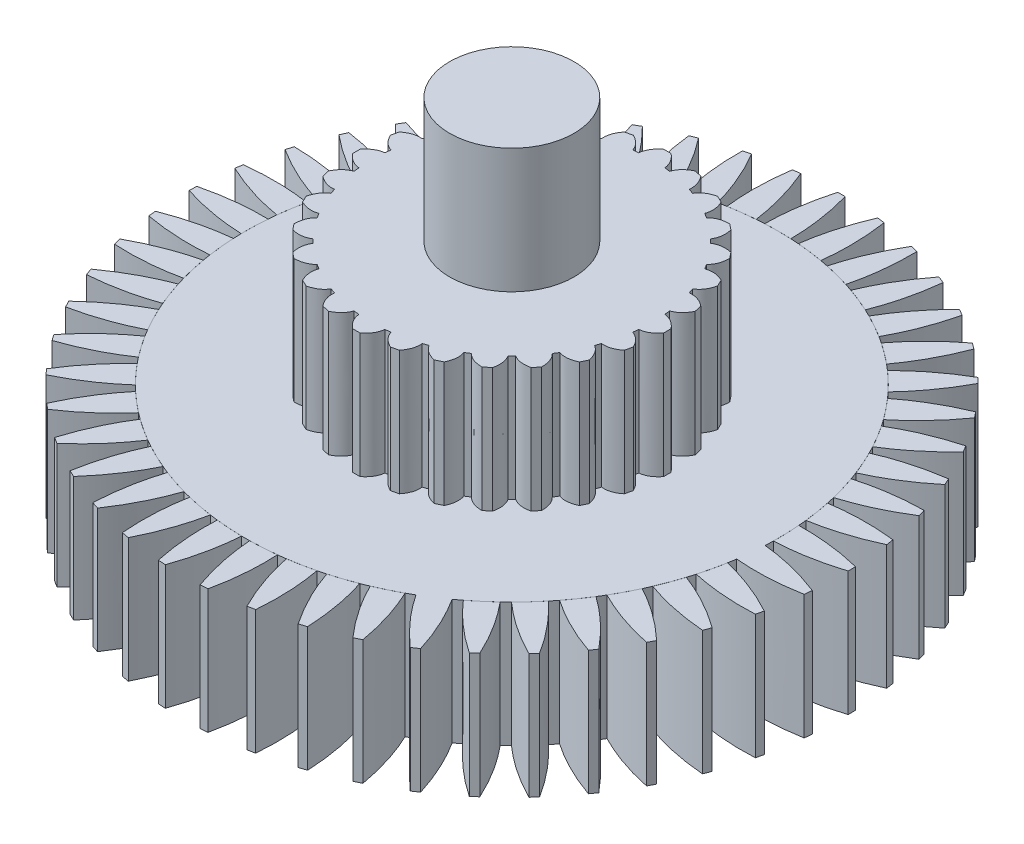
SolidWorks part; units mm, degrees
ref_plane "Front Plane" through (0, 0, 0) normal (0, 0, 1) x (1, 0, 0)
ref_plane "Top Plane" through (0, 0, 0) normal (0, 1, 0) x (1, 0, 0)
ref_plane "Right Plane" through (0, 0, 0) normal (1, 0, 0) x (0, 0, -1)
sketch "Sketch1" plane through (0, 0, 0) normal (0, 1, 0) x (1, 0, 0)
  line L0 (0, 2.5799) -> (0, -0.2416) construction
  line L1 (0.105, 2.4922) -> (0.105, 1.9026) construction
  line L2 (-0.03, 2.65) -> (0.03, 2.65)
  line L3 (0.3091, 2.6321) -> (0.3686, 2.6244)
  line L4 (0.6432, 2.5709) -> (0.7012, 2.5557)
  line L5 (0.9667, 2.4676) -> (1.0223, 2.4451)
  line L6 (1.2743, 2.3237) -> (1.3265, 2.2943)
  line L7 (1.561, 2.1417) -> (1.609, 2.1058)
  line L8 (1.822, 1.9245) -> (1.8651, 1.8828)
  line L9 (2.0531, 1.6757) -> (2.0906, 1.6288)
  line L10 (2.2506, 1.3994) -> (2.2817, 1.3481)
  line L11 (2.411, 1.1001) -> (2.4353, 1.0452)
  line L12 (2.5319, 0.7828) -> (2.549, 0.7252)
  line L13 (2.6112, 0.4526) -> (2.6208, 0.3933)
  line L14 (2.6477, 0.1149) -> (2.6496, 0.055)
  line L15 (2.6406, -0.2246) -> (2.6349, -0.2843)
  line L16 (2.5902, -0.5604) -> (2.5769, -0.6189)
  line L17 (2.4973, -0.8871) -> (2.4766, -0.9434)
  line L18 (2.3634, -1.1991) -> (2.3356, -1.2523)
  line L19 (2.1906, -1.4915) -> (2.1563, -1.5407)
  line L20 (1.9819, -1.7594) -> (1.9416, -1.8038)
  line L21 (1.7406, -1.9984) -> (1.695, -2.0373)
  line L22 (1.4708, -2.2046) -> (1.4205, -2.2373)
  line L23 (1.1768, -2.3746) -> (1.1228, -2.4006)
  line L24 (0.8635, -2.5055) -> (0.8066, -2.5245)
  line L25 (0.536, -2.5954) -> (0.4771, -2.6069)
  line L26 (0.1997, -2.6426) -> (0.1398, -2.6465)
  line L27 (-0.1398, -2.6465) -> (-0.1997, -2.6426)
  line L28 (-0.4771, -2.6069) -> (-0.536, -2.5954)
  line L29 (-0.8066, -2.5245) -> (-0.8635, -2.5055)
  line L30 (-1.1228, -2.4006) -> (-1.1768, -2.3746)
  line L31 (-1.4205, -2.2373) -> (-1.4708, -2.2046)
  line L32 (-1.695, -2.0373) -> (-1.7406, -1.9984)
  line L33 (-1.9416, -1.8038) -> (-1.9819, -1.7594)
  line L34 (-2.1563, -1.5407) -> (-2.1906, -1.4915)
  line L35 (-2.3356, -1.2523) -> (-2.3634, -1.1991)
  line L36 (-2.4766, -0.9434) -> (-2.4973, -0.8871)
  line L37 (-2.5769, -0.6189) -> (-2.5902, -0.5604)
  line L38 (-2.6349, -0.2843) -> (-2.6406, -0.2246)
  line L39 (-2.6496, 0.055) -> (-2.6477, 0.1149)
  line L40 (-2.6208, 0.3933) -> (-2.6112, 0.4526)
  line L41 (-2.549, 0.7252) -> (-2.5319, 0.7828)
  line L42 (-2.4353, 1.0452) -> (-2.411, 1.1001)
  line L43 (-2.2817, 1.3481) -> (-2.2506, 1.3994)
  line L44 (-2.0906, 1.6288) -> (-2.0531, 1.6757)
  line L45 (-1.8651, 1.8828) -> (-1.822, 1.9245)
  line L46 (-1.609, 2.1058) -> (-1.561, 2.1417)
  line L47 (-1.3265, 2.2943) -> (-1.2743, 2.3237)
  line L48 (-1.0223, 2.4451) -> (-0.9667, 2.4676)
  line L49 (-0.7012, 2.5557) -> (-0.6432, 2.5709)
  line L50 (-0.3686, 2.6244) -> (-0.3091, 2.6321)
  circle A0 centre (0, 0) radius 2.14
  spline S0 degree 2 poles (0.03, 2.65) (0.1023, 2.3962) (0.105, 2.1374) knots 0 0 0 0.927528 0.927528 0.927528
  spline S1 degree 1 poles (0, 2.14) (0.105, 2.1374) knots 0 0 1 1
  spline S2 degree 1 poles (0, 2.14) (-0.105, 2.1374) knots 0 0 1 1
  spline S3 degree 2 poles (-0.03, 2.65) (-0.1023, 2.3962) (-0.105, 2.1374) knots 0 0 0 0.927528 0.927528 0.927528
  spline S4 degree 1 poles (0.2737, 2.1224) (0.1692, 2.1333) knots 0 0 1 1
  spline S5 degree 1 poles (0.2737, 2.1224) (0.3775, 2.1064) knots 0 0 1 1
  spline S6 degree 2 poles (0.3091, 2.6321) (0.205, 2.3896) (0.1692, 2.1333) knots 0 0 0 0.927528 0.927528 0.927528
  spline S7 degree 2 poles (0.3686, 2.6244) (0.4079, 2.3635) (0.3775, 2.1064) knots 0 0 0 0.927528 0.927528 0.927528
  spline S8 degree 1 poles (0.5428, 2.07) (0.4406, 2.0942) knots 0 0 1 1
  spline S9 degree 1 poles (0.5428, 2.07) (0.6437, 2.0409) knots 0 0 1 1
  spline S10 degree 2 poles (0.6432, 2.5709) (0.5089, 2.3438) (0.4406, 2.0942) knots 0 0 0 0.927528 0.927528 0.927528
  spline S11 degree 2 poles (0.7012, 2.5557) (0.7068, 2.2919) (0.6437, 2.0409) knots 0 0 0 0.927528 0.927528 0.927528
  spline S12 degree 1 poles (0.8031, 1.9836) (0.7048, 2.0206) knots 0 0 1 1
  spline S13 degree 1 poles (0.8031, 1.9836) (0.8994, 1.9418) knots 0 0 1 1
  spline S14 degree 2 poles (0.9667, 2.4676) (0.8044, 2.2595) (0.7048, 2.0206) knots 0 0 0 0.927528 0.927528 0.927528
  spline S15 degree 2 poles (1.0223, 2.4451) (0.994, 2.1827) (0.8994, 1.9418) knots 0 0 0 0.927528 0.927528 0.927528
  spline S16 degree 1 poles (1.0501, 1.8646) (0.9574, 1.9139) knots 0 0 1 1
  spline S17 degree 1 poles (1.0501, 1.8646) (1.1404, 1.8109) knots 0 0 1 1
  spline S18 degree 2 poles (1.2743, 2.3237) (1.0868, 2.1381) (0.9574, 1.9139) knots 0 0 0 0.927528 0.927528 0.927528
  spline S19 degree 2 poles (1.3265, 2.2943) (1.265, 2.0377) (1.1404, 1.8109) knots 0 0 0 0.927528 0.927528 0.927528
  spline S20 degree 1 poles (1.28, 1.715) (1.1943, 1.7758) knots 0 0 1 1
  spline S21 degree 1 poles (1.28, 1.715) (1.3626, 1.6502) knots 0 0 1 1
  spline S22 degree 2 poles (1.561, 2.1417) (1.3512, 1.9816) (1.1943, 1.7758) knots 0 0 0 0.927528 0.927528 0.927528
  spline S23 degree 2 poles (1.609, 2.1058) (1.5152, 1.8592) (1.3626, 1.6502) knots 0 0 0 0.927528 0.927528 0.927528
  spline S24 degree 1 poles (1.4888, 1.5373) (1.4115, 1.6085) knots 0 0 1 1
  spline S25 degree 1 poles (1.4888, 1.5373) (1.5624, 1.4624) knots 0 0 1 1
  spline S26 degree 2 poles (1.822, 1.9245) (1.5935, 1.7925) (1.4115, 1.6085) knots 0 0 0 0.927528 0.927528 0.927528
  spline S27 degree 2 poles (1.8651, 1.8828) (1.7405, 1.6502) (1.5624, 1.4624) knots 0 0 0 0.927528 0.927528 0.927528
  spline S28 degree 1 poles (1.6731, 1.3343) (1.6056, 1.4148) knots 0 0 1 1
  spline S29 degree 1 poles (1.6731, 1.3343) (1.7366, 1.2506) knots 0 0 1 1
  spline S30 degree 2 poles (2.0531, 1.6757) (1.8097, 1.574) (1.6056, 1.4148) knots 0 0 0 0.927528 0.927528 0.927528
  spline S31 degree 2 poles (2.0906, 1.6288) (1.9372, 1.4141) (1.7366, 1.2506) knots 0 0 0 0.927528 0.927528 0.927528
  spline S32 degree 1 poles (1.83, 1.1094) (1.7734, 1.1978) knots 0 0 1 1
  spline S33 degree 1 poles (1.83, 1.1094) (1.8822, 1.0182) knots 0 0 1 1
  spline S34 degree 2 poles (2.2506, 1.3994) (1.9961, 1.3297) (1.7734, 1.1978) knots 0 0 0 0.927528 0.927528 0.927528
  spline S35 degree 2 poles (2.2817, 1.3481) (2.1022, 1.1547) (1.8822, 1.0182) knots 0 0 0 0.927528 0.927528 0.927528
  spline S36 degree 1 poles (1.9568, 0.8662) (1.912, 0.9612) knots 0 0 1 1
  spline S37 degree 1 poles (1.9568, 0.8662) (1.997, 0.7692) knots 0 0 1 1
  spline S38 degree 2 poles (2.411, 1.1001) (2.1498, 1.0635) (1.912, 0.9612) knots 0 0 0 0.927528 0.927528 0.927528
  spline S39 degree 2 poles (2.4353, 1.0452) (2.2326, 0.8764) (1.997, 0.7692) knots 0 0 0 0.927528 0.927528 0.927528
  spline S40 degree 1 poles (2.0515, 0.6089) (2.0192, 0.7088) knots 0 0 1 1
  spline S41 degree 1 poles (2.0515, 0.6089) (2.079, 0.5075) knots 0 0 1 1
  spline S42 degree 2 poles (2.5319, 0.7828) (2.2681, 0.7799) (2.0192, 0.7088) knots 0 0 0 0.927528 0.927528 0.927528
  spline S43 degree 2 poles (2.549, 0.7252) (2.3263, 0.5837) (2.079, 0.5075) knots 0 0 0 0.927528 0.927528 0.927528
  spline S44 degree 1 poles (2.1126, 0.3415) (2.0933, 0.4448) knots 0 0 1 1
  spline S45 degree 1 poles (2.1126, 0.3415) (2.1268, 0.2375) knots 0 0 1 1
  spline S46 degree 2 poles (2.6112, 0.4526) (2.3492, 0.4834) (2.0933, 0.4448) knots 0 0 0 0.927528 0.927528 0.927528
  spline S47 degree 2 poles (2.6208, 0.3933) (2.3819, 0.2815) (2.1268, 0.2375) knots 0 0 0 0.927528 0.927528 0.927528
  spline S48 degree 1 poles (2.1389, 0.0686) (2.133, 0.1735) knots 0 0 1 1
  spline S49 degree 1 poles (2.1389, 0.0686) (2.1397, -0.0364) knots 0 0 1 1
  spline S50 degree 2 poles (2.6477, 0.1149) (2.3917, 0.179) (2.133, 0.1735) knots 0 0 0 0.927528 0.927528 0.927528
  spline S51 degree 2 poles (2.6496, 0.055) (2.3983, -0.0254) (2.1397, -0.0364) knots 0 0 0 0.927528 0.927528 0.927528
  spline S52 degree 1 poles (2.1301, -0.2055) (2.1376, -0.1007) knots 0 0 1 1
  spline S53 degree 1 poles (2.1301, -0.2055) (2.1175, -0.3098) knots 0 0 1 1
  spline S54 degree 2 poles (2.6406, -0.2246) (2.395, -0.1283) (2.1376, -0.1007) knots 0 0 0 0.927528 0.927528 0.927528
  spline S55 degree 2 poles (2.6349, -0.2843) (2.3753, -0.3319) (2.1175, -0.3098) knots 0 0 0 0.927528 0.927528 0.927528
  spline S56 degree 1 poles (2.0863, -0.4762) (2.1072, -0.3733) knots 0 0 1 1
  spline S57 degree 1 poles (2.0863, -0.4762) (2.0605, -0.578) knots 0 0 1 1
  spline S58 degree 2 poles (2.5902, -0.5604) (2.3589, -0.4335) (2.1072, -0.3733) knots 0 0 0 0.927528 0.927528 0.927528
  spline S59 degree 2 poles (2.5769, -0.6189) (2.3134, -0.6329) (2.0605, -0.578) knots 0 0 0 0.927528 0.927528 0.927528
  spline S60 degree 1 poles (2.0083, -0.7391) (2.0422, -0.6397) knots 0 0 1 1
  spline S61 degree 1 poles (2.0083, -0.7391) (1.9696, -0.8367) knots 0 0 1 1
  spline S62 degree 2 poles (2.4973, -0.8871) (2.2841, -0.7316) (2.0422, -0.6397) knots 0 0 0 0.927528 0.927528 0.927528
  spline S63 degree 2 poles (2.4766, -0.9434) (2.2135, -0.9236) (1.9696, -0.8367) knots 0 0 0 0.927528 0.927528 0.927528
  spline S64 degree 1 poles (1.8973, -0.9898) (1.9436, -0.8955) knots 0 0 1 1
  spline S65 degree 1 poles (1.8973, -0.9898) (1.8465, -1.0817) knots 0 0 1 1
  spline S66 degree 2 poles (2.3634, -1.1991) (2.1718, -1.0177) (1.9436, -0.8955) knots 0 0 0 0.927528 0.927528 0.927528
  spline S67 degree 2 poles (2.3356, -1.2523) (2.0772, -1.199) (1.8465, -1.0817) knots 0 0 0 0.927528 0.927528 0.927528
  spline S68 degree 1 poles (1.7552, -1.2243) (1.8131, -1.1367) knots 0 0 1 1
  spline S69 degree 1 poles (1.7552, -1.2243) (1.693, -1.309) knots 0 0 1 1
  spline S70 degree 2 poles (2.1906, -1.4915) (2.0238, -1.287) (1.8131, -1.1367) knots 0 0 0 0.927528 0.927528 0.927528
  spline S71 degree 2 poles (2.1563, -1.5407) (1.9068, -1.4548) (1.693, -1.309) knots 0 0 0 0.927528 0.927528 0.927528
  spline S72 degree 1 poles (1.5842, -1.4387) (1.6529, -1.3593) knots 0 0 1 1
  spline S73 degree 1 poles (1.5842, -1.4387) (1.5117, -1.5147) knots 0 0 1 1
  spline S74 degree 2 poles (1.9819, -1.7594) (1.8427, -1.5353) (1.6529, -1.3593) knots 0 0 0 0.927528 0.927528 0.927528
  spline S75 degree 2 poles (1.9416, -1.8038) (1.7051, -1.6867) (1.5117, -1.5147) knots 0 0 0 0.927528 0.927528 0.927528
  spline S76 degree 1 poles (1.3872, -1.6295) (1.4655, -1.5595) knots 0 0 1 1
  spline S77 degree 1 poles (1.3872, -1.6295) (1.3056, -1.6956) knots 0 0 1 1
  spline S78 degree 2 poles (1.7406, -1.9984) (1.6312, -1.7583) (1.4655, -1.5595) knots 0 0 0 0.927528 0.927528 0.927528
  spline S79 degree 2 poles (1.695, -2.0373) (1.4754, -1.8909) (1.3056, -1.6956) knots 0 0 0 0.927528 0.927528 0.927528
  spline S80 degree 1 poles (1.1674, -1.7935) (1.254, -1.7341) knots 0 0 1 1
  spline S81 degree 1 poles (1.1674, -1.7935) (1.078, -1.8486) knots 0 0 1 1
  spline S82 degree 2 poles (1.4708, -2.2046) (1.393, -1.9525) (1.254, -1.7341) knots 0 0 0 0.927528 0.927528 0.927528
  spline S83 degree 2 poles (1.4205, -2.2373) (1.2215, -2.0641) (1.078, -1.8486) knots 0 0 0 0.927528 0.927528 0.927528
  spline S84 degree 1 poles (0.9285, -1.9281) (1.022, -1.8802) knots 0 0 1 1
  spline S85 degree 1 poles (0.9285, -1.9281) (0.8328, -1.9713) knots 0 0 1 1
  spline S86 degree 2 poles (1.1768, -2.3746) (1.1318, -2.1146) (1.022, -1.8802) knots 0 0 0 0.927528 0.927528 0.927528
  spline S87 degree 2 poles (1.1228, -2.4006) (0.9475, -2.2033) (0.8328, -1.9713) knots 0 0 0 0.927528 0.927528 0.927528
  spline S88 degree 1 poles (0.6743, -2.031) (0.7732, -1.9954) knots 0 0 1 1
  spline S89 degree 1 poles (0.6743, -2.031) (0.5739, -2.0616) knots 0 0 1 1
  spline S90 degree 2 poles (0.8635, -2.5055) (0.8521, -2.2419) (0.7732, -1.9954) knots 0 0 0 0.927528 0.927528 0.927528
  spline S91 degree 2 poles (0.8066, -2.5245) (0.658, -2.3064) (0.5739, -2.0616) knots 0 0 0 0.927528 0.927528 0.927528
  spline S92 degree 1 poles (0.4091, -2.1005) (0.5117, -2.0779) knots 0 0 1 1
  spline S93 degree 1 poles (0.4091, -2.1005) (0.3055, -2.1181) knots 0 0 1 1
  spline S94 degree 2 poles (0.536, -2.5954) (0.5585, -2.3325) (0.5117, -2.0779) knots 0 0 0 0.927528 0.927528 0.927528
  spline S95 degree 2 poles (0.4771, -2.6069) (0.3577, -2.3716) (0.3055, -2.1181) knots 0 0 0 0.927528 0.927528 0.927528
  spline S96 degree 1 poles (0.1371, -2.1356) (0.2417, -2.1263) knots 0 0 1 1
  spline S97 degree 1 poles (0.1371, -2.1356) (0.0322, -2.1398) knots 0 0 1 1
  spline S98 degree 2 poles (0.1997, -2.6426) (0.2556, -2.3848) (0.2417, -2.1263) knots 0 0 0 0.927528 0.927528 0.927528
  spline S99 degree 2 poles (0.1398, -2.6465) (0.0515, -2.3979) (0.0322, -2.1398) knots 0 0 0 0.927528 0.927528 0.927528
  spline S100 degree 1 poles (-0.1371, -2.1356) (-0.0322, -2.1398) knots 0 0 1 1
  spline S101 degree 1 poles (-0.1371, -2.1356) (-0.2417, -2.1263) knots 0 0 1 1
  spline S102 degree 2 poles (-0.1398, -2.6465) (-0.0515, -2.3979) (-0.0322, -2.1398) knots 0 0 0 0.927528 0.927528 0.927528
  spline S103 degree 2 poles (-0.1997, -2.6426) (-0.2556, -2.3848) (-0.2417, -2.1263) knots 0 0 0 0.927528 0.927528 0.927528
  spline S104 degree 1 poles (-0.4091, -2.1005) (-0.3055, -2.1181) knots 0 0 1 1
  spline S105 degree 1 poles (-0.4091, -2.1005) (-0.5117, -2.0779) knots 0 0 1 1
  spline S106 degree 2 poles (-0.4771, -2.6069) (-0.3577, -2.3716) (-0.3055, -2.1181) knots 0 0 0 0.927528 0.927528 0.927528
  spline S107 degree 2 poles (-0.536, -2.5954) (-0.5585, -2.3325) (-0.5117, -2.0779) knots 0 0 0 0.927528 0.927528 0.927528
  spline S108 degree 1 poles (-0.6743, -2.031) (-0.5739, -2.0616) knots 0 0 1 1
  spline S109 degree 1 poles (-0.6743, -2.031) (-0.7732, -1.9954) knots 0 0 1 1
  spline S110 degree 2 poles (-0.8066, -2.5245) (-0.658, -2.3064) (-0.5739, -2.0616) knots 0 0 0 0.927528 0.927528 0.927528
  spline S111 degree 2 poles (-0.8635, -2.5055) (-0.8521, -2.2419) (-0.7732, -1.9954) knots 0 0 0 0.927528 0.927528 0.927528
  spline S112 degree 1 poles (-0.9285, -1.9281) (-0.8328, -1.9713) knots 0 0 1 1
  spline S113 degree 1 poles (-0.9285, -1.9281) (-1.022, -1.8802) knots 0 0 1 1
  spline S114 degree 2 poles (-1.1228, -2.4006) (-0.9475, -2.2033) (-0.8328, -1.9713) knots 0 0 0 0.927528 0.927528 0.927528
  spline S115 degree 2 poles (-1.1768, -2.3746) (-1.1318, -2.1146) (-1.022, -1.8802) knots 0 0 0 0.927528 0.927528 0.927528
  spline S116 degree 1 poles (-1.1674, -1.7935) (-1.078, -1.8486) knots 0 0 1 1
  spline S117 degree 1 poles (-1.1674, -1.7935) (-1.254, -1.7341) knots 0 0 1 1
  spline S118 degree 2 poles (-1.4205, -2.2373) (-1.2215, -2.0641) (-1.078, -1.8486) knots 0 0 0 0.927528 0.927528 0.927528
  spline S119 degree 2 poles (-1.4708, -2.2046) (-1.393, -1.9525) (-1.254, -1.7341) knots 0 0 0 0.927528 0.927528 0.927528
  spline S120 degree 1 poles (-1.3872, -1.6295) (-1.3056, -1.6956) knots 0 0 1 1
  spline S121 degree 1 poles (-1.3872, -1.6295) (-1.4655, -1.5595) knots 0 0 1 1
  spline S122 degree 2 poles (-1.695, -2.0373) (-1.4754, -1.8909) (-1.3056, -1.6956) knots 0 0 0 0.927528 0.927528 0.927528
  spline S123 degree 2 poles (-1.7406, -1.9984) (-1.6312, -1.7583) (-1.4655, -1.5595) knots 0 0 0 0.927528 0.927528 0.927528
  spline S124 degree 1 poles (-1.5842, -1.4387) (-1.5117, -1.5147) knots 0 0 1 1
  spline S125 degree 1 poles (-1.5842, -1.4387) (-1.6529, -1.3593) knots 0 0 1 1
  spline S126 degree 2 poles (-1.9416, -1.8038) (-1.7051, -1.6867) (-1.5117, -1.5147) knots 0 0 0 0.927528 0.927528 0.927528
  spline S127 degree 2 poles (-1.9819, -1.7594) (-1.8427, -1.5353) (-1.6529, -1.3593) knots 0 0 0 0.927528 0.927528 0.927528
  spline S128 degree 1 poles (-1.7552, -1.2243) (-1.693, -1.309) knots 0 0 1 1
  spline S129 degree 1 poles (-1.7552, -1.2243) (-1.8131, -1.1367) knots 0 0 1 1
  spline S130 degree 2 poles (-2.1563, -1.5407) (-1.9068, -1.4548) (-1.693, -1.309) knots 0 0 0 0.927528 0.927528 0.927528
  spline S131 degree 2 poles (-2.1906, -1.4915) (-2.0238, -1.287) (-1.8131, -1.1367) knots 0 0 0 0.927528 0.927528 0.927528
  spline S132 degree 1 poles (-1.8973, -0.9898) (-1.8465, -1.0817) knots 0 0 1 1
  spline S133 degree 1 poles (-1.8973, -0.9898) (-1.9436, -0.8955) knots 0 0 1 1
  spline S134 degree 2 poles (-2.3356, -1.2523) (-2.0772, -1.199) (-1.8465, -1.0817) knots 0 0 0 0.927528 0.927528 0.927528
  spline S135 degree 2 poles (-2.3634, -1.1991) (-2.1718, -1.0177) (-1.9436, -0.8955) knots 0 0 0 0.927528 0.927528 0.927528
  spline S136 degree 1 poles (-2.0083, -0.7391) (-1.9696, -0.8367) knots 0 0 1 1
  spline S137 degree 1 poles (-2.0083, -0.7391) (-2.0422, -0.6397) knots 0 0 1 1
  spline S138 degree 2 poles (-2.4766, -0.9434) (-2.2135, -0.9236) (-1.9696, -0.8367) knots 0 0 0 0.927528 0.927528 0.927528
  spline S139 degree 2 poles (-2.4973, -0.8871) (-2.2841, -0.7316) (-2.0422, -0.6397) knots 0 0 0 0.927528 0.927528 0.927528
  spline S140 degree 1 poles (-2.0863, -0.4762) (-2.0605, -0.578) knots 0 0 1 1
  spline S141 degree 1 poles (-2.0863, -0.4762) (-2.1072, -0.3733) knots 0 0 1 1
  spline S142 degree 2 poles (-2.5769, -0.6189) (-2.3134, -0.6329) (-2.0605, -0.578) knots 0 0 0 0.927528 0.927528 0.927528
  spline S143 degree 2 poles (-2.5902, -0.5604) (-2.3589, -0.4335) (-2.1072, -0.3733) knots 0 0 0 0.927528 0.927528 0.927528
  spline S144 degree 1 poles (-2.1301, -0.2055) (-2.1175, -0.3098) knots 0 0 1 1
  spline S145 degree 1 poles (-2.1301, -0.2055) (-2.1376, -0.1007) knots 0 0 1 1
  spline S146 degree 2 poles (-2.6349, -0.2843) (-2.3753, -0.3319) (-2.1175, -0.3098) knots 0 0 0 0.927528 0.927528 0.927528
  spline S147 degree 2 poles (-2.6406, -0.2246) (-2.395, -0.1283) (-2.1376, -0.1007) knots 0 0 0 0.927528 0.927528 0.927528
  spline S148 degree 1 poles (-2.1389, 0.0686) (-2.1397, -0.0364) knots 0 0 1 1
  spline S149 degree 1 poles (-2.1389, 0.0686) (-2.133, 0.1735) knots 0 0 1 1
  spline S150 degree 2 poles (-2.6496, 0.055) (-2.3983, -0.0254) (-2.1397, -0.0364) knots 0 0 0 0.927528 0.927528 0.927528
  spline S151 degree 2 poles (-2.6477, 0.1149) (-2.3917, 0.179) (-2.133, 0.1735) knots 0 0 0 0.927528 0.927528 0.927528
  spline S152 degree 1 poles (-2.1126, 0.3415) (-2.1268, 0.2375) knots 0 0 1 1
  spline S153 degree 1 poles (-2.1126, 0.3415) (-2.0933, 0.4448) knots 0 0 1 1
  spline S154 degree 2 poles (-2.6208, 0.3933) (-2.3819, 0.2815) (-2.1268, 0.2375) knots 0 0 0 0.927528 0.927528 0.927528
  spline S155 degree 2 poles (-2.6112, 0.4526) (-2.3492, 0.4834) (-2.0933, 0.4448) knots 0 0 0 0.927528 0.927528 0.927528
  spline S156 degree 1 poles (-2.0515, 0.6089) (-2.079, 0.5075) knots 0 0 1 1
  spline S157 degree 1 poles (-2.0515, 0.6089) (-2.0192, 0.7088) knots 0 0 1 1
  spline S158 degree 2 poles (-2.549, 0.7252) (-2.3263, 0.5837) (-2.079, 0.5075) knots 0 0 0 0.927528 0.927528 0.927528
  spline S159 degree 2 poles (-2.5319, 0.7828) (-2.2681, 0.7799) (-2.0192, 0.7088) knots 0 0 0 0.927528 0.927528 0.927528
  spline S160 degree 1 poles (-1.9568, 0.8662) (-1.997, 0.7692) knots 0 0 1 1
  spline S161 degree 1 poles (-1.9568, 0.8662) (-1.912, 0.9612) knots 0 0 1 1
  spline S162 degree 2 poles (-2.4353, 1.0452) (-2.2326, 0.8764) (-1.997, 0.7692) knots 0 0 0 0.927528 0.927528 0.927528
  spline S163 degree 2 poles (-2.411, 1.1001) (-2.1498, 1.0635) (-1.912, 0.9612) knots 0 0 0 0.927528 0.927528 0.927528
  spline S164 degree 1 poles (-1.83, 1.1094) (-1.8822, 1.0182) knots 0 0 1 1
  spline S165 degree 1 poles (-1.83, 1.1094) (-1.7734, 1.1978) knots 0 0 1 1
  spline S166 degree 2 poles (-2.2817, 1.3481) (-2.1022, 1.1547) (-1.8822, 1.0182) knots 0 0 0 0.927528 0.927528 0.927528
  spline S167 degree 2 poles (-2.2506, 1.3994) (-1.9961, 1.3297) (-1.7734, 1.1978) knots 0 0 0 0.927528 0.927528 0.927528
  spline S168 degree 1 poles (-1.6731, 1.3343) (-1.7366, 1.2506) knots 0 0 1 1
  spline S169 degree 1 poles (-1.6731, 1.3343) (-1.6056, 1.4148) knots 0 0 1 1
  spline S170 degree 2 poles (-2.0906, 1.6288) (-1.9372, 1.4141) (-1.7366, 1.2506) knots 0 0 0 0.927528 0.927528 0.927528
  spline S171 degree 2 poles (-2.0531, 1.6757) (-1.8097, 1.574) (-1.6056, 1.4148) knots 0 0 0 0.927528 0.927528 0.927528
  spline S172 degree 1 poles (-1.4888, 1.5373) (-1.5624, 1.4624) knots 0 0 1 1
  spline S173 degree 1 poles (-1.4888, 1.5373) (-1.4115, 1.6085) knots 0 0 1 1
  spline S174 degree 2 poles (-1.8651, 1.8828) (-1.7405, 1.6502) (-1.5624, 1.4624) knots 0 0 0 0.927528 0.927528 0.927528
  spline S175 degree 2 poles (-1.822, 1.9245) (-1.5935, 1.7925) (-1.4115, 1.6085) knots 0 0 0 0.927528 0.927528 0.927528
  spline S176 degree 1 poles (-1.28, 1.715) (-1.3626, 1.6502) knots 0 0 1 1
  spline S177 degree 1 poles (-1.28, 1.715) (-1.1943, 1.7758) knots 0 0 1 1
  spline S178 degree 2 poles (-1.609, 2.1058) (-1.5152, 1.8592) (-1.3626, 1.6502) knots 0 0 0 0.927528 0.927528 0.927528
  spline S179 degree 2 poles (-1.561, 2.1417) (-1.3512, 1.9816) (-1.1943, 1.7758) knots 0 0 0 0.927528 0.927528 0.927528
  spline S180 degree 1 poles (-1.0501, 1.8646) (-1.1404, 1.8109) knots 0 0 1 1
  spline S181 degree 1 poles (-1.0501, 1.8646) (-0.9574, 1.9139) knots 0 0 1 1
  spline S182 degree 2 poles (-1.3265, 2.2943) (-1.265, 2.0377) (-1.1404, 1.8109) knots 0 0 0 0.927528 0.927528 0.927528
  spline S183 degree 2 poles (-1.2743, 2.3237) (-1.0868, 2.1381) (-0.9574, 1.9139) knots 0 0 0 0.927528 0.927528 0.927528
  spline S184 degree 1 poles (-0.8031, 1.9836) (-0.8994, 1.9418) knots 0 0 1 1
  spline S185 degree 1 poles (-0.8031, 1.9836) (-0.7048, 2.0206) knots 0 0 1 1
  spline S186 degree 2 poles (-1.0223, 2.4451) (-0.994, 2.1827) (-0.8994, 1.9418) knots 0 0 0 0.927528 0.927528 0.927528
  spline S187 degree 2 poles (-0.9667, 2.4676) (-0.8044, 2.2595) (-0.7048, 2.0206) knots 0 0 0 0.927528 0.927528 0.927528
  spline S188 degree 1 poles (-0.5428, 2.07) (-0.6437, 2.0409) knots 0 0 1 1
  spline S189 degree 1 poles (-0.5428, 2.07) (-0.4406, 2.0942) knots 0 0 1 1
  spline S190 degree 2 poles (-0.7012, 2.5557) (-0.7068, 2.2919) (-0.6437, 2.0409) knots 0 0 0 0.927528 0.927528 0.927528
  spline S191 degree 2 poles (-0.6432, 2.5709) (-0.5089, 2.3438) (-0.4406, 2.0942) knots 0 0 0 0.927528 0.927528 0.927528
  spline S192 degree 1 poles (-0.2737, 2.1224) (-0.3775, 2.1064) knots 0 0 1 1
  spline S193 degree 1 poles (-0.2737, 2.1224) (-0.1692, 2.1333) knots 0 0 1 1
  spline S194 degree 2 poles (-0.3686, 2.6244) (-0.4079, 2.3635) (-0.3775, 2.1064) knots 0 0 0 0.927528 0.927528 0.927528
  spline S195 degree 2 poles (-0.3091, 2.6321) (-0.205, 2.3896) (-0.1692, 2.1333) knots 0 0 0 0.927528 0.927528 0.927528
  point P13 (0, 2.65)
  dimension "D1" = 4.28
  dimension "D2" = 0.105
  dimension "D3" = 0.03
  dimension "D4" = 2.65
  dimension "D5" = 49
extrude "Boss-Extrude1" add sketch "Sketch1" along normal blind 1 contours S193 S192 A0 S189 S188 S185 S184 S181 S180 S177 S176 S173 S172 S169 S168 S165 S164 S161 S160 S157 S156 S153 S152 S149 S148 S145 S144 S141 S140 S137 S136 S133 S132 S129 S128 | S87 L23 S86 A0 | S79 L21 S78 A0 | S75 L20 S74 A0 | S71 L19 S70 A0 | S67 L18 S66 A0 | S63 L17 S62 A0 | S59 L16 S58 A0 | S51 L14 S50 A0 | S47 L13 S46 A0 | S43 L12 S42 A0 | S39 L11 S38 A0 | S35 L10 S34 A0 | S31 L9 S30 A0 | S27 L8 S26 A0 | S23 L7 S22 A0 | S19 L6 S18 A0 | S15 L5 S14 A0 | S91 L24 S90 A0 | S95 L25 S94 A0 | S99 L26 S98 A0 | S103 L27 S102 A0 | S107 L28 S106 A0 | S111 L29 S110 A0 | S115 L30 S114 A0 | S119 L31 S118 A0 | S123 L32 S122 A0 | S127 L33 S126 A0 | S131 L34 S130 A0 | S135 L35 S134 A0 | S139 L36 S138 A0 | S143 L37 S142 A0 | S147 L38 S146 A0 | S151 L39 S150 A0 | S155 L40 S154 A0 | S159 L41 S158 A0 | S163 L42 S162 A0 | S167 L43 S166 A0 | S171 L44 S170 A0 | S175 L45 S174 A0 | S179 L46 S178 A0 | S183 L47 S182 A0 | S187 L48 S186 A0 | S191 L49 S190 A0 | S195 L50 S194 A0 | S11 L4 S10 A0 | S7 L3 S6 A0 | L2 S3 A0 S0 | S83 S81 S80 S82 L22 | S54 S52 S53 S55 L15 region at (0, 0, -2.3543) region at (0, 0, 0) region at (-0.3011, 0, -2.335) region at (0.3011, 0, -2.335) region at (-0.5972, 0, -2.2773) region at (0.5972, 0, -2.2773) region at (-0.8835, 0, -2.1822) region at (0.8835, 0, -2.1822) region at (-1.1553, 0, -2.0513) region at (1.1553, 0, -2.0513) region at (-1.4081, 0, -1.8868) region at (1.4081, 0, -1.8868) region at (-1.6378, 0, -1.6912) region at (1.6378, 0, -1.6912) region at (-1.8407, 0, -1.4679) region at (1.8407, 0, -1.4679) region at (-2.0133, 0, -1.2205) region at (2.0133, 0, -1.2205) region at (-2.1528, 0, -0.953) region at (2.1528, 0, -0.953) region at (-2.257, 0, -0.6699) region at (2.257, 0, -0.6699) region at (-2.3241, 0, -0.3757) region at (2.3241, 0, -0.3757) region at (-2.3531, 0, -0.0755) region at (2.3531, 0, -0.0755) region at (-2.3434, 0, 0.2261) region at (-2.2953, 0, 0.5239) region at (2.2953, 0, 0.5239) region at (-2.2094, 0, 0.8131) region at (2.2094, 0, 0.8131) region at (-2.0873, 0, 1.089) region at (2.0873, 0, 1.089) region at (-1.9309, 0, 1.3469) region at (1.9309, 0, 1.3469) region at (-1.7428, 0, 1.5828) region at (1.7428, 0, 1.5828) region at (-1.5261, 0, 1.7927) region at (1.5261, 0, 1.7927) region at (-1.2844, 0, 1.9731) region at (-1.0215, 0, 2.1212) region at (1.0215, 0, 2.1212) region at (-0.7419, 0, 2.2344) region at (0.7419, 0, 2.2344) region at (-0.45, 0, 2.3109) region at (0.45, 0, 2.3109) region at (-0.1508, 0, 2.3495) region at (0.1508, 0, 2.3495)
sketch "Sketch2" plane through (0, 1, 0) normal (0, 1, 0) x (1, 0, 0)
  circle A1 centre (0, 0) radius 1.13
  dimension "D1" = 2.26
extrude "Boss-Extrude11" add sketch "Sketch2" along normal blind 1
sketch "Sketch3" plane through (0, 2, 0) normal (0, 1, 0) x (1, 0, 0)
  line L0 (0, 1.3367) -> (0, 0.8013) construction
  line L1 (0.105, 1.2872) -> (0.105, 0.9526) construction
  line L2 (-0.03, 1.25) -> (0.03, 1.25)
  line L3 (0.2489, 1.2253) -> (0.3074, 1.212)
  line L4 (0.5153, 1.1392) -> (0.5694, 1.1132)
  line L5 (0.7559, 0.996) -> (0.8028, 0.9586)
  line L6 (0.9586, 0.8028) -> (0.996, 0.7559)
  line L7 (1.1132, 0.5694) -> (1.1392, 0.5153)
  line L8 (1.212, 0.3074) -> (1.2253, 0.2489)
  line L9 (1.25, 0.03) -> (1.25, -0.03)
  line L10 (1.2253, -0.2489) -> (1.212, -0.3074)
  line L11 (1.1392, -0.5153) -> (1.1132, -0.5694)
  line L12 (0.996, -0.7559) -> (0.9586, -0.8028)
  line L13 (0.8028, -0.9586) -> (0.7559, -0.996)
  line L14 (0.5694, -1.1132) -> (0.5153, -1.1392)
  line L15 (0.3074, -1.212) -> (0.2489, -1.2253)
  line L16 (0.03, -1.25) -> (-0.03, -1.25)
  line L17 (-0.2489, -1.2253) -> (-0.3074, -1.212)
  line L18 (-0.5153, -1.1392) -> (-0.5694, -1.1132)
  line L19 (-0.7559, -0.996) -> (-0.8028, -0.9586)
  line L20 (-0.9586, -0.8028) -> (-0.996, -0.7559)
  line L21 (-1.1132, -0.5694) -> (-1.1392, -0.5153)
  line L22 (-1.212, -0.3074) -> (-1.2253, -0.2489)
  line L23 (-1.25, -0.03) -> (-1.25, 0.03)
  line L24 (-1.2253, 0.2489) -> (-1.212, 0.3074)
  line L25 (-1.1392, 0.5153) -> (-1.1132, 0.5694)
  line L26 (-0.996, 0.7559) -> (-0.9586, 0.8028)
  line L27 (-0.8028, 0.9586) -> (-0.7559, 0.996)
  line L28 (-0.5694, 1.1132) -> (-0.5153, 1.1392)
  line L29 (-0.3074, 1.212) -> (-0.2489, 1.2253)
  circle A0 centre (0, 0) radius 1.13 construction
  spline S0 degree 2 poles (0.03, 1.25) (0.1004, 1.1938) (0.105, 1.1199) knots 0 0 0 0.878063 0.878063 0.878063
  spline S1 degree 1 poles (0, 1.13) (0.105, 1.1199) knots 0 0 1 1
  spline S2 degree 1 poles (0, 1.13) (-0.105, 1.1199) knots 0 0 1 1
  spline S3 degree 2 poles (-0.03, 1.25) (-0.1004, 1.1938) (-0.105, 1.1199) knots 0 0 0 0.878063 0.878063 0.878063
  spline S4 degree 1 poles (0.2514, 1.1017) (0.1468, 1.1152) knots 0 0 1 1
  spline S5 degree 1 poles (0.2514, 1.1017) (0.3516, 1.0685) knots 0 0 1 1
  spline S6 degree 2 poles (0.3074, 1.212) (0.3635, 1.1415) (0.3516, 1.0685) knots 0 0 0 0.878063 0.878063 0.878063
  spline S7 degree 2 poles (0.2489, 1.2253) (0.1677, 1.1862) (0.1468, 1.1152) knots 0 0 0 0.878063 0.878063 0.878063
  spline S8 degree 1 poles (0.4903, 1.0181) (0.3913, 1.0546) knots 0 0 1 1
  spline S9 degree 1 poles (0.4903, 1.0181) (0.5805, 0.9634) knots 0 0 1 1
  spline S10 degree 2 poles (0.5694, 1.1132) (0.6084, 1.032) (0.5805, 0.9634) knots 0 0 0 0.878063 0.878063 0.878063
  spline S11 degree 2 poles (0.5153, 1.1392) (0.4275, 1.1191) (0.3913, 1.0546) knots 0 0 0 0.878063 0.878063 0.878063
  spline S12 degree 1 poles (0.7045, 0.8835) (0.6162, 0.941) knots 0 0 1 1
  spline S13 degree 1 poles (0.7045, 0.8835) (0.7803, 0.8101) knots 0 0 1 1
  spline S14 degree 2 poles (0.8028, 0.9586) (0.8228, 0.8707) (0.7803, 0.8101) knots 0 0 0 0.878063 0.878063 0.878063
  spline S15 degree 2 poles (0.7559, 0.996) (0.6658, 0.9959) (0.6162, 0.941) knots 0 0 0 0.878063 0.878063 0.878063
  spline S16 degree 1 poles (0.8835, 0.7045) (0.8101, 0.7803) knots 0 0 1 1
  spline S17 degree 1 poles (0.8835, 0.7045) (0.941, 0.6162) knots 0 0 1 1
  spline S18 degree 2 poles (0.996, 0.7559) (0.9959, 0.6658) (0.941, 0.6162) knots 0 0 0 0.878063 0.878063 0.878063
  spline S19 degree 2 poles (0.9586, 0.8028) (0.8707, 0.8228) (0.8101, 0.7803) knots 0 0 0 0.878063 0.878063 0.878063
  spline S20 degree 1 poles (1.0181, 0.4903) (0.9634, 0.5805) knots 0 0 1 1
  spline S21 degree 1 poles (1.0181, 0.4903) (1.0546, 0.3913) knots 0 0 1 1
  spline S22 degree 2 poles (1.1392, 0.5153) (1.1191, 0.4275) (1.0546, 0.3913) knots 0 0 0 0.878063 0.878063 0.878063
  spline S23 degree 2 poles (1.1132, 0.5694) (1.032, 0.6084) (0.9634, 0.5805) knots 0 0 0 0.878063 0.878063 0.878063
  spline S24 degree 1 poles (1.1017, 0.2514) (1.0685, 0.3516) knots 0 0 1 1
  spline S25 degree 1 poles (1.1017, 0.2514) (1.1152, 0.1468) knots 0 0 1 1
  spline S26 degree 2 poles (1.2253, 0.2489) (1.1862, 0.1677) (1.1152, 0.1468) knots 0 0 0 0.878063 0.878063 0.878063
  spline S27 degree 2 poles (1.212, 0.3074) (1.1415, 0.3635) (1.0685, 0.3516) knots 0 0 0 0.878063 0.878063 0.878063
  spline S28 degree 1 poles (1.13, 0) (1.1199, 0.105) knots 0 0 1 1
  spline S29 degree 1 poles (1.13, 0) (1.1199, -0.105) knots 0 0 1 1
  spline S30 degree 2 poles (1.25, -0.03) (1.1938, -0.1004) (1.1199, -0.105) knots 0 0 0 0.878063 0.878063 0.878063
  spline S31 degree 2 poles (1.25, 0.03) (1.1938, 0.1004) (1.1199, 0.105) knots 0 0 0 0.878063 0.878063 0.878063
  spline S32 degree 1 poles (1.1017, -0.2514) (1.1152, -0.1468) knots 0 0 1 1
  spline S33 degree 1 poles (1.1017, -0.2514) (1.0685, -0.3516) knots 0 0 1 1
  spline S34 degree 2 poles (1.212, -0.3074) (1.1415, -0.3635) (1.0685, -0.3516) knots 0 0 0 0.878063 0.878063 0.878063
  spline S35 degree 2 poles (1.2253, -0.2489) (1.1862, -0.1677) (1.1152, -0.1468) knots 0 0 0 0.878063 0.878063 0.878063
  spline S36 degree 1 poles (1.0181, -0.4903) (1.0546, -0.3913) knots 0 0 1 1
  spline S37 degree 1 poles (1.0181, -0.4903) (0.9634, -0.5805) knots 0 0 1 1
  spline S38 degree 2 poles (1.1132, -0.5694) (1.032, -0.6084) (0.9634, -0.5805) knots 0 0 0 0.878063 0.878063 0.878063
  spline S39 degree 2 poles (1.1392, -0.5153) (1.1191, -0.4275) (1.0546, -0.3913) knots 0 0 0 0.878063 0.878063 0.878063
  spline S40 degree 1 poles (0.8835, -0.7045) (0.941, -0.6162) knots 0 0 1 1
  spline S41 degree 1 poles (0.8835, -0.7045) (0.8101, -0.7803) knots 0 0 1 1
  spline S42 degree 2 poles (0.9586, -0.8028) (0.8707, -0.8228) (0.8101, -0.7803) knots 0 0 0 0.878063 0.878063 0.878063
  spline S43 degree 2 poles (0.996, -0.7559) (0.9959, -0.6658) (0.941, -0.6162) knots 0 0 0 0.878063 0.878063 0.878063
  spline S44 degree 1 poles (0.7045, -0.8835) (0.7803, -0.8101) knots 0 0 1 1
  spline S45 degree 1 poles (0.7045, -0.8835) (0.6162, -0.941) knots 0 0 1 1
  spline S46 degree 2 poles (0.7559, -0.996) (0.6658, -0.9959) (0.6162, -0.941) knots 0 0 0 0.878063 0.878063 0.878063
  spline S47 degree 2 poles (0.8028, -0.9586) (0.8228, -0.8707) (0.7803, -0.8101) knots 0 0 0 0.878063 0.878063 0.878063
  spline S48 degree 1 poles (0.4903, -1.0181) (0.5805, -0.9634) knots 0 0 1 1
  spline S49 degree 1 poles (0.4903, -1.0181) (0.3913, -1.0546) knots 0 0 1 1
  spline S50 degree 2 poles (0.5153, -1.1392) (0.4275, -1.1191) (0.3913, -1.0546) knots 0 0 0 0.878063 0.878063 0.878063
  spline S51 degree 2 poles (0.5694, -1.1132) (0.6084, -1.032) (0.5805, -0.9634) knots 0 0 0 0.878063 0.878063 0.878063
  spline S52 degree 1 poles (0.2514, -1.1017) (0.3516, -1.0685) knots 0 0 1 1
  spline S53 degree 1 poles (0.2514, -1.1017) (0.1468, -1.1152) knots 0 0 1 1
  spline S54 degree 2 poles (0.2489, -1.2253) (0.1677, -1.1862) (0.1468, -1.1152) knots 0 0 0 0.878063 0.878063 0.878063
  spline S55 degree 2 poles (0.3074, -1.212) (0.3635, -1.1415) (0.3516, -1.0685) knots 0 0 0 0.878063 0.878063 0.878063
  spline S56 degree 1 poles (0, -1.13) (0.105, -1.1199) knots 0 0 1 1
  spline S57 degree 1 poles (0, -1.13) (-0.105, -1.1199) knots 0 0 1 1
  spline S58 degree 2 poles (-0.03, -1.25) (-0.1004, -1.1938) (-0.105, -1.1199) knots 0 0 0 0.878063 0.878063 0.878063
  spline S59 degree 2 poles (0.03, -1.25) (0.1004, -1.1938) (0.105, -1.1199) knots 0 0 0 0.878063 0.878063 0.878063
  spline S60 degree 1 poles (-0.2514, -1.1017) (-0.1468, -1.1152) knots 0 0 1 1
  spline S61 degree 1 poles (-0.2514, -1.1017) (-0.3516, -1.0685) knots 0 0 1 1
  spline S62 degree 2 poles (-0.3074, -1.212) (-0.3635, -1.1415) (-0.3516, -1.0685) knots 0 0 0 0.878063 0.878063 0.878063
  spline S63 degree 2 poles (-0.2489, -1.2253) (-0.1677, -1.1862) (-0.1468, -1.1152) knots 0 0 0 0.878063 0.878063 0.878063
  spline S64 degree 1 poles (-0.4903, -1.0181) (-0.3913, -1.0546) knots 0 0 1 1
  spline S65 degree 1 poles (-0.4903, -1.0181) (-0.5805, -0.9634) knots 0 0 1 1
  spline S66 degree 2 poles (-0.5694, -1.1132) (-0.6084, -1.032) (-0.5805, -0.9634) knots 0 0 0 0.878063 0.878063 0.878063
  spline S67 degree 2 poles (-0.5153, -1.1392) (-0.4275, -1.1191) (-0.3913, -1.0546) knots 0 0 0 0.878063 0.878063 0.878063
  spline S68 degree 1 poles (-0.7045, -0.8835) (-0.6162, -0.941) knots 0 0 1 1
  spline S69 degree 1 poles (-0.7045, -0.8835) (-0.7803, -0.8101) knots 0 0 1 1
  spline S70 degree 2 poles (-0.8028, -0.9586) (-0.8228, -0.8707) (-0.7803, -0.8101) knots 0 0 0 0.878063 0.878063 0.878063
  spline S71 degree 2 poles (-0.7559, -0.996) (-0.6658, -0.9959) (-0.6162, -0.941) knots 0 0 0 0.878063 0.878063 0.878063
  spline S72 degree 1 poles (-0.8835, -0.7045) (-0.8101, -0.7803) knots 0 0 1 1
  spline S73 degree 1 poles (-0.8835, -0.7045) (-0.941, -0.6162) knots 0 0 1 1
  spline S74 degree 2 poles (-0.996, -0.7559) (-0.9959, -0.6658) (-0.941, -0.6162) knots 0 0 0 0.878063 0.878063 0.878063
  spline S75 degree 2 poles (-0.9586, -0.8028) (-0.8707, -0.8228) (-0.8101, -0.7803) knots 0 0 0 0.878063 0.878063 0.878063
  spline S76 degree 1 poles (-1.0181, -0.4903) (-0.9634, -0.5805) knots 0 0 1 1
  spline S77 degree 1 poles (-1.0181, -0.4903) (-1.0546, -0.3913) knots 0 0 1 1
  spline S78 degree 2 poles (-1.1392, -0.5153) (-1.1191, -0.4275) (-1.0546, -0.3913) knots 0 0 0 0.878063 0.878063 0.878063
  spline S79 degree 2 poles (-1.1132, -0.5694) (-1.032, -0.6084) (-0.9634, -0.5805) knots 0 0 0 0.878063 0.878063 0.878063
  spline S80 degree 1 poles (-1.1017, -0.2514) (-1.0685, -0.3516) knots 0 0 1 1
  spline S81 degree 1 poles (-1.1017, -0.2514) (-1.1152, -0.1468) knots 0 0 1 1
  spline S82 degree 2 poles (-1.2253, -0.2489) (-1.1862, -0.1677) (-1.1152, -0.1468) knots 0 0 0 0.878063 0.878063 0.878063
  spline S83 degree 2 poles (-1.212, -0.3074) (-1.1415, -0.3635) (-1.0685, -0.3516) knots 0 0 0 0.878063 0.878063 0.878063
  spline S84 degree 1 poles (-1.13, 0) (-1.1199, -0.105) knots 0 0 1 1
  spline S85 degree 1 poles (-1.13, 0) (-1.1199, 0.105) knots 0 0 1 1
  spline S86 degree 2 poles (-1.25, 0.03) (-1.1938, 0.1004) (-1.1199, 0.105) knots 0 0 0 0.878063 0.878063 0.878063
  spline S87 degree 2 poles (-1.25, -0.03) (-1.1938, -0.1004) (-1.1199, -0.105) knots 0 0 0 0.878063 0.878063 0.878063
  spline S88 degree 1 poles (-1.1017, 0.2514) (-1.1152, 0.1468) knots 0 0 1 1
  spline S89 degree 1 poles (-1.1017, 0.2514) (-1.0685, 0.3516) knots 0 0 1 1
  spline S90 degree 2 poles (-1.212, 0.3074) (-1.1415, 0.3635) (-1.0685, 0.3516) knots 0 0 0 0.878063 0.878063 0.878063
  spline S91 degree 2 poles (-1.2253, 0.2489) (-1.1862, 0.1677) (-1.1152, 0.1468) knots 0 0 0 0.878063 0.878063 0.878063
  spline S92 degree 1 poles (-1.0181, 0.4903) (-1.0546, 0.3913) knots 0 0 1 1
  spline S93 degree 1 poles (-1.0181, 0.4903) (-0.9634, 0.5805) knots 0 0 1 1
  spline S94 degree 2 poles (-1.1132, 0.5694) (-1.032, 0.6084) (-0.9634, 0.5805) knots 0 0 0 0.878063 0.878063 0.878063
  spline S95 degree 2 poles (-1.1392, 0.5153) (-1.1191, 0.4275) (-1.0546, 0.3913) knots 0 0 0 0.878063 0.878063 0.878063
  spline S96 degree 1 poles (-0.8835, 0.7045) (-0.941, 0.6162) knots 0 0 1 1
  spline S97 degree 1 poles (-0.8835, 0.7045) (-0.8101, 0.7803) knots 0 0 1 1
  spline S98 degree 2 poles (-0.9586, 0.8028) (-0.8707, 0.8228) (-0.8101, 0.7803) knots 0 0 0 0.878063 0.878063 0.878063
  spline S99 degree 2 poles (-0.996, 0.7559) (-0.9959, 0.6658) (-0.941, 0.6162) knots 0 0 0 0.878063 0.878063 0.878063
  spline S100 degree 1 poles (-0.7045, 0.8835) (-0.7803, 0.8101) knots 0 0 1 1
  spline S101 degree 1 poles (-0.7045, 0.8835) (-0.6162, 0.941) knots 0 0 1 1
  spline S102 degree 2 poles (-0.7559, 0.996) (-0.6658, 0.9959) (-0.6162, 0.941) knots 0 0 0 0.878063 0.878063 0.878063
  spline S103 degree 2 poles (-0.8028, 0.9586) (-0.8228, 0.8707) (-0.7803, 0.8101) knots 0 0 0 0.878063 0.878063 0.878063
  spline S104 degree 1 poles (-0.4903, 1.0181) (-0.5805, 0.9634) knots 0 0 1 1
  spline S105 degree 1 poles (-0.4903, 1.0181) (-0.3913, 1.0546) knots 0 0 1 1
  spline S106 degree 2 poles (-0.5153, 1.1392) (-0.4275, 1.1191) (-0.3913, 1.0546) knots 0 0 0 0.878063 0.878063 0.878063
  spline S107 degree 2 poles (-0.5694, 1.1132) (-0.6084, 1.032) (-0.5805, 0.9634) knots 0 0 0 0.878063 0.878063 0.878063
  spline S108 degree 1 poles (-0.2514, 1.1017) (-0.3516, 1.0685) knots 0 0 1 1
  spline S109 degree 1 poles (-0.2514, 1.1017) (-0.1468, 1.1152) knots 0 0 1 1
  spline S110 degree 2 poles (-0.2489, 1.2253) (-0.1677, 1.1862) (-0.1468, 1.1152) knots 0 0 0 0.878063 0.878063 0.878063
  spline S111 degree 2 poles (-0.3074, 1.212) (-0.3635, 1.1415) (-0.3516, 1.0685) knots 0 0 0 0.878063 0.878063 0.878063
  point P13 (0, 1.25)
  dimension "D1" = 0.105
  dimension "D2" = 0.03
  dimension "D3" = 1.25
extrude "Boss-Extrude12" add sketch "Sketch3" against normal blind 1
sketch "Sketch4" plane through (0, 2, 0) normal (0, 1, 0) x (1, 0, 0)
  circle A0 centre (0, 0) radius 0.5
  dimension "D1" = 1
extrude "Boss-Extrude13" add sketch "Sketch4" along normal blind 1
sketch "Sketch5" plane through (0, 0, 0) normal (0, -1, 0) x (1, 0, 0)
  circle A0 centre (0, 0) radius 0.5
  dimension "D1" = 1
extrude "Boss-Extrude14" add sketch "Sketch5" along normal blind 1
